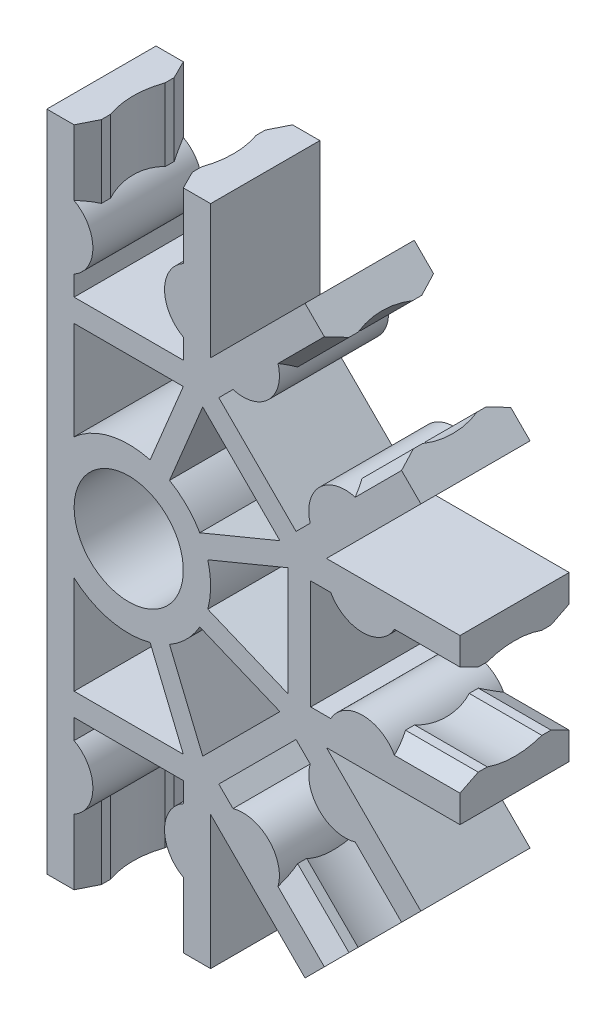
SolidWorks part; units mm, degrees
ref_plane "前视基准面" through (0, 0, 0) normal (0, 0, 1) x (1, 0, 0)
ref_plane "上视基准面" through (0, 0, 0) normal (0, 1, 0) x (1, 0, 0)
ref_plane "右视基准面" through (0, 0, 0) normal (1, 0, 0) x (0, 0, -1)
sketch "草图1" plane through (0, 0, 0) normal (0, 0, 1) x (1, 0, 0)
  line L0 (-4.5, 0) -> (-4.5, -18.2)
  line L1 (4.5, 0) -> (4.5, -18.2)
  line L2 (-4.5, -18.2) -> (-3, -18.2)
  line L3 (-3, -18.2) -> (-3, -14.6)
  line L4 (4.5, -18.2) -> (3, -18.2)
  line L5 (3, -18.2) -> (3, -14.6)
  line L6 (-3, -11.1) -> (-3, -10)
  line L7 (-3, -10) -> (3, -10)
  line L8 (3, -10) -> (3, -11.1)
  arc A0 (4.5, 0) -> (-4.5, 0) centre (0, 0) ccw
  arc A1 (-3, -11.1) -> (-3, -14.6) centre (-3.9682, -12.85) cw
  arc A2 (3, -11.1) -> (3, -14.6) centre (3.9682, -12.85) ccw
  point P1 (0, 4.5)
  dimension "D1" = 9
  dimension "D10" = 14.5
  dimension "D11" = 2
  dimension "D12" = 2
  dimension "D2" = 18.2
  dimension "D3" = 18.2
  dimension "D4" = 1.5
  dimension "D5" = 1.5
  dimension "D6" = 1.1
  dimension "D7" = 1.1
  dimension "D8" = 3.5
  dimension "D9" = 3.5
extrude "凸台-拉伸1" add sketch "草图1" along normal blind 6
sketch "草图3" plane through (0, -18.2, 0) normal (0, -1, 0) x (1, 0, 0)
  line L0 (-3, 6) -> (-3, 0)
  line L1 (-3, 0) -> (-2.5, 1)
  line L2 (-2.5, 1) -> (-2.5, 1.5)
  line L3 (-3, 6) -> (-2.5, 5)
  line L4 (-2.5, 5) -> (-2.5, 4.5)
  line L5 (0, 0) -> (0, 6.4845) construction
  line L6 (3, 0) -> (2.5, 1)
  line L7 (2.5, 1) -> (2.5, 1.5)
  line L8 (2.5, 5) -> (2.5, 4.5)
  line L9 (3, 6) -> (2.5, 5)
  line L10 (3, 6) -> (3, 0)
  arc A0 (-2.5, 1.5) -> (-2.5, 4.5) centre (1.7426, 3) cw
  arc A1 (2.5, 1.5) -> (2.5, 4.5) centre (-1.7426, 3) ccw
  dimension "D7" = 4.5
  dimension "D1" = 0.5
  dimension "D2" = 0.5
  dimension "D3" = 0.5
  dimension "D4" = 0.5
  dimension "D5" = 1.5
  dimension "D6" = 1.5
extrude "凸台-拉伸2" add sketch "草图3" against normal up to next
ref_axis "Axis" through (0, 0, 0) along (0, 0, 1)
pattern_circular "阵列(圆周)1" count 5 every 45 about axis through (0, 0, 0) along (0, 0, 1) of "凸台-拉伸1", "凸台-拉伸2"
sketch "草图4" plane through (0, 0, 0) normal (0, 0, -1) x (-1, 0, 0)
  line L0 (3, -8.75) -> (3, -3.3541)
  line L1 (3, -8.75) -> (-3, -8.75)
  line L2 (-3, -8.75) -> (-1.1749, -4.3439)
  line L3 (0, 0) -> (-4.5, -10.864) construction
  line L4 (3, -10) -> (-3, -10) construction
  line L5 (0, 0) -> (-10.864, -4.5) construction
  line L6 (-4.0659, -8.3085) -> (-8.3085, -4.0659)
  line L7 (-4.9497, -9.1924) -> (-9.1924, -4.9497) construction
  line L8 (0, 0) -> (-7.0711, -7.0711) construction
  line L9 (-8.3085, -4.0659) -> (-3.9024, -2.2408)
  line L10 (-4.0659, -8.3085) -> (-2.2408, -3.9024)
  line L11 (0, 0) -> (-10, 0) construction
  line L12 (-10, -3) -> (-10, 3) construction
  line L13 (3, 8.75) -> (3, 3.3541)
  line L14 (3, 8.75) -> (-3, 8.75)
  line L15 (-3, 8.75) -> (-1.1749, 4.3439)
  line L16 (-8.75, 3) -> (-4.3439, 1.1749)
  line L17 (-8.75, -3) -> (-8.75, 3)
  line L18 (-8.75, -3) -> (-4.3439, -1.1749)
  line L19 (-4.0659, 8.3085) -> (-2.2408, 3.9024)
  line L20 (-8.3085, 4.0659) -> (-4.0659, 8.3085)
  line L21 (-8.3085, 4.0659) -> (-3.9024, 2.2408)
  circle A0 centre (0, 0) radius 3
  arc A1 (-2.2408, 3.9024) -> (-3.9024, 2.2408) centre (0, 0) ccw
  arc A2 (-4.3439, 1.1749) -> (-4.3439, -1.1749) centre (0, 0) ccw
  arc A3 (-3.9024, -2.2408) -> (-2.2408, -3.9024) centre (0, 0) ccw
  arc A4 (-1.1749, -4.3439) -> (3, -3.3541) centre (0, 0) ccw
  arc A5 (3, 3.3541) -> (-1.1749, 4.3439) centre (0, 0) ccw
  point P5 (-6.1872, -6.1872)
  point P41 (0, 0)
  dimension "D1" = 6
  dimension "D2" = 9
  dimension "D3" = 6
  dimension "D4" = 1.25
  dimension "D5" = 6
  dimension "D6" = 1.25
  dimension "D7" = 3
extrude "切除-拉伸1" cut sketch "草图4" against normal through all
